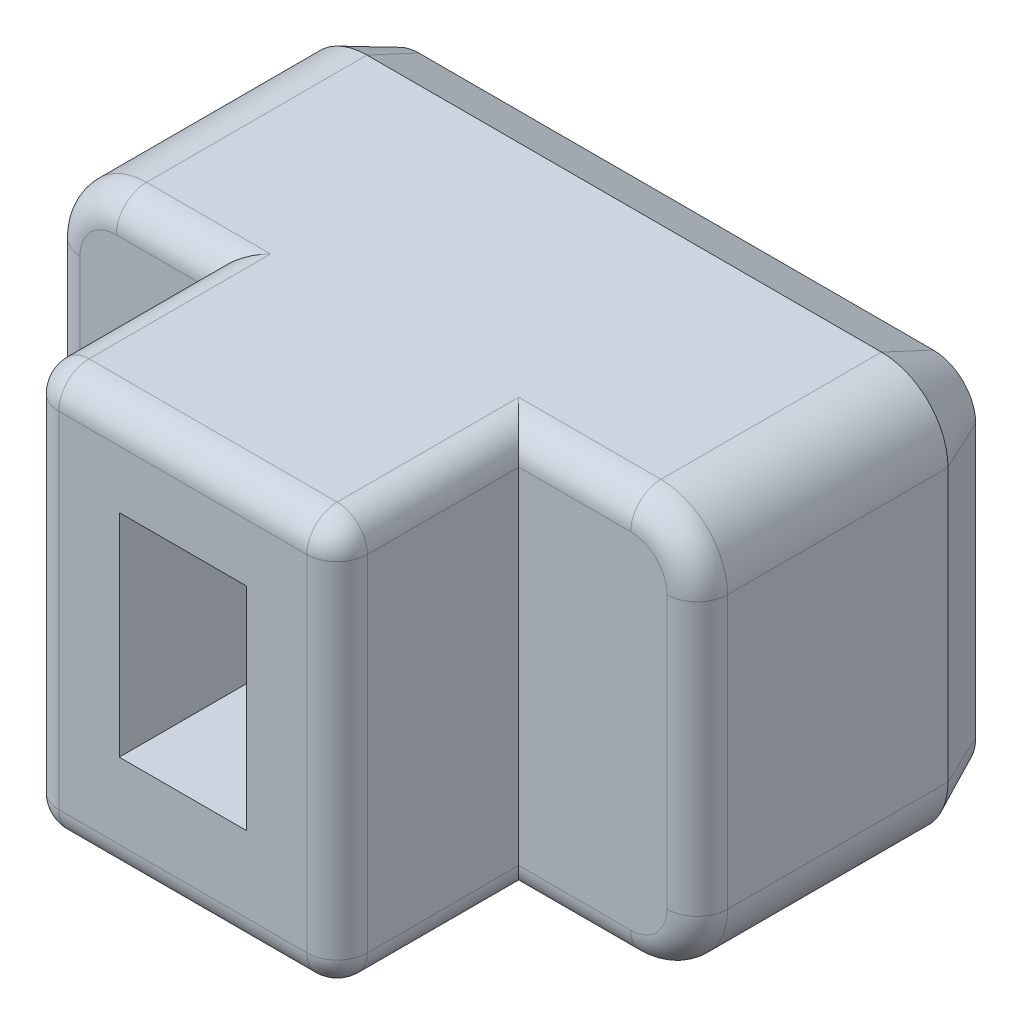
SolidWorks part; units mm, degrees
ref_plane "Plan de face" through (0, 0, 0) normal (0, 0, 1) x (1, 0, 0)
ref_plane "Plan de dessus" through (0, 0, 0) normal (0, 1, 0) x (1, 0, 0)
ref_plane "Plan de droite" through (0, 0, 0) normal (1, 0, 0) x (0, 0, -1)
sketch "Esquisse2" plane through (0, 0, 0) normal (0, 0, 1) x (1, 0, 0)
  line L1 (1.1, 0) -> (9.6, 0)
  line L2 (0, 1.1) -> (0, 5.6)
  line L3 (1.1, 6.7) -> (9.6, 6.7)
  line L4 (10.7, 1.1) -> (10.7, 5.6)
  arc A0 (9.6, 6.7) -> (10.7, 5.6) centre (9.6, 5.6) cw
  arc A1 (9.6, 0) -> (10.7, 1.1) centre (9.6, 1.1) ccw
  arc A2 (1.1, 0) -> (0, 1.1) centre (1.1, 1.1) cw
  arc A3 (0, 5.6) -> (1.1, 6.7) centre (1.1, 5.6) cw
  point P7 (10.7, 6.7)
  point P12 (0, 0)
  point P15 (0, 6.7)
  dimension "D3" = 1.1
  dimension "D1" = 10.7
  dimension "D2" = 6.7
extrude "Boss.-Extru.1" add sketch "Esquisse2" along normal blind 8
sketch "Esquisse3" plane through (0, 0, 8) normal (0, 0, 1) x (1, 0, 0)
  line L0 (0, 5.6) -> (0, 1.1) construction
  line L1 (4.15, 5.25) -> (6.25, 5.25)
  line L2 (4.15, 5.25) -> (4.15, 1.75)
  line L3 (4.15, 1.75) -> (6.25, 1.75)
  line L4 (6.25, 5.25) -> (6.25, 1.75)
  line L5 (10.7, 1.1) -> (10.7, 5.6) construction
  line L6 (9.6, 6.7) -> (1.1, 6.7) construction
  line L7 (1.1, 0) -> (9.6, 0) construction
  dimension "D1" = 2.1
  dimension "D2" = 3.5
  dimension "D3" = 4.15
  dimension "D4" = 4.45
  dimension "D5" = 1.45
  dimension "D6" = 1.75
extrude "Enlèv. mat.-Extru.1" cut sketch "Esquisse3" against normal blind 3
sketch "Esquisse4" plane through (0, 0, 8) normal (0, 0, 1) x (1, 0, 0)
  line L0 (2.65, 6.7) -> (2.65, 0)
  line L1 (9.6, 6.7) -> (1.1, 6.7) construction
  line L2 (1.1, 0) -> (9.6, 0) construction
  line L3 (2.65, 0) -> (7.75, 0)
  line L4 (7.75, 0) -> (7.75, 6.7)
  line L5 (7.75, 6.7) -> (2.65, 6.7)
  line L6 (4.15, 5.25) -> (4.15, 1.75) construction
  line L7 (6.25, 1.75) -> (6.25, 5.25) construction
  dimension "D1" = 1.5
  dimension "D2" = 1.5
extrude "Enlèv. mat.-Extru.2" cut sketch "Esquisse4" against normal blind 3 flip side to cut
fillet "Congé1" radius 0.5 18 edges at (8.675, 0, 5) (10.3778, 0.3222, 5) (10.7, 3.35, 5) (10.3778, 6.3778, 5) (1.875, 6.7, 5) (0.3222, 6.3778, 5) (1.875, 0, 5) (0.3222, 0.3222, 5) (7.75, 6.7, 6.5) (2.65, 6.7, 6.5) (7.75, 0, 6.5) (2.65, 0, 6.5) (2.65, 3.35, 8) (5.2, 6.7, 8) (7.75, 3.35, 8) (5.2, 0, 8) (8.675, 6.7, 5) (0, 3.35, 5)
chamfer "Chanfrein1" distance 0.4 angle 65 8 edges at (5.35, 0, 0) (10.3778, 0.3222, 0) (0.3222, 0.3222, 0) (10.7, 3.35, 0) (0, 3.35, 0) (10.3778, 6.3778, 0) (0.3222, 6.3778, 0) (5.35, 6.7, 0) first distance on face at (5.35, 3.35, 0)
ref_plane "Plan1" through (0, 0, 0.2) normal (0, 0, 1) x (1, 0, 0)
sketch "Esquisse5" plane through (0, 0, 0.2) normal (0, 0, 1) x (1, 0, 0)
  line L0 (-0.9378, 5.3566) -> (11.6517, 5.3566) construction
  text T0 "HDG" font "Century Gothic" height 4
extrude "Enlèv. mat.-Extru.3" cut sketch "Esquisse5" against normal blind 0.3
extrude "Boss.-Extru.2" add sketch "Esquisse5<3>" against normal blind 0.2 from offset 0.2 offset against normal yes
sketch "Esquisse5<3>" plane through (0, 0, 0.2) normal (0, 0, 1) x (1, 0, 0) same geometry as "Esquisse5"
